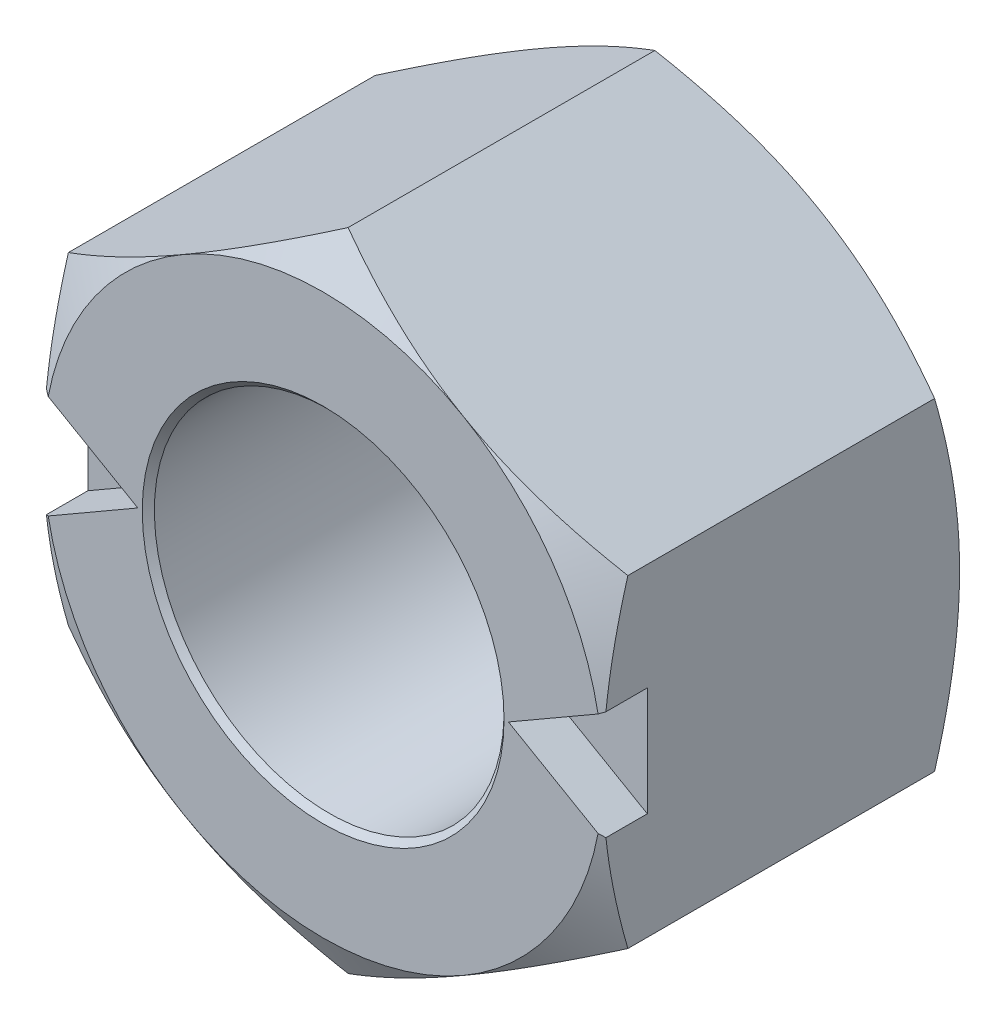
SolidWorks part; units mm, degrees
ref_plane "Front Plane" through (0, 0, 0) normal (0, 0, 1) x (1, 0, 0)
ref_plane "Top Plane" through (0, 0, 0) normal (0, 1, 0) x (1, 0, 0)
ref_plane "Right Plane" through (0, 0, 0) normal (1, 0, 0) x (0, 0, -1)
sketch "Sketch1" plane through (0, 0, 0) normal (0, 0, 1) x (1, 0, 0)
  line L0 (0.3175, 0) -> (-0.3175, 0) construction
  line L1 (0, 4.6188) -> (-4, 2.3094) construction
  line L2 (-4, 2.3094) -> (-4, -2.3094) construction
  line L3 (-4, -2.3094) -> (0, -4.6188) construction
  line L4 (0, -4.6188) -> (4, -2.3094) construction
  line L5 (4, -2.3094) -> (4, 2.3094) construction
  line L6 (4, 2.3094) -> (0, 4.6188) construction
  circle A0 centre (0, 0) radius 4 construction
  point P10 (4, 2.3094)
  point P11 (-4, 2.3094)
  point P14 (0, 0)
  point P15 (-0.3175, 0)
  point P16 (0.3175, 0)
  dimension "Hex Width" = 8
  dimension "Cut Depth" = 0.635
sketch "Sketch2" plane through (0, 0, 0) normal (1, 0, 0) x (0, 0, -1)
  line L0 (2.55, 4.6188) -> (-2.55, 4.6188) construction
  line L1 (2.55, -4.6188) -> (-2.55, -4.6188) construction
  line L3 (2.55, 0) -> (-2.55, 0) construction
  line L5 (-2.55, -2.5) -> (-2.55, 2.5) construction
  line L6 (2.55, -2.5) -> (2.55, 2.5) construction
  line L7 (-3.3, 2.5866) -> (-2.5, 2.5866) construction
  line L8 (-2.5, 2.5866) -> (-2.9, 1.8938) construction
  line L9 (-2.9, 1.8938) -> (-3.3, 2.5866) construction
  line L10 (-2.9, 1.8938) -> (-2.9, 1.9804) construction
  line L11 (-2.85, 1.9804) -> (-2.95, 1.9804) construction
  line L12 (-3.275, 2.5433) -> (-2.525, 2.5433) construction
  line L13 (-3.25, 2.5) -> (-2.55, 2.5) construction
  line L14 (-2.9, 2.5) -> (-2.9, 2.5866) construction
  line L15 (-2.55, 2.5) -> (2.55, 2.5) construction
  line L16 (-2.55, -2.5) -> (2.55, -2.5) construction
  line L17 (-2.4634, 2.5) -> (-2.55, 2.5866) construction
  line L18 (2.4634, 2.5) -> (2.55, 2.5866) construction
  line L20 (0, 4.6188) -> (0, -4.6188) construction
  point P0 (0, -4.6188)
  point P2 (0, 4.6188)
  point P4 (2.55, 4.6188)
  point P7 (0, 4.6188)
  point P8 (-2.55, 4.6188)
  point P10 (-2.55, -4.6188)
  point P13 (0, -4.6188)
  point P14 (2.55, -4.6188)
  point P15 (-2.55, 0)
  point P18 (0, 0)
  point P19 (2.55, 0)
  point P21 (-2.55, 2.5)
  point P24 (-2.55, 0)
  point P25 (-2.55, -2.5)
  point P28 (2.55, 0)
  point P29 (2.55, -2.5)
  point P30 (2.55, 2.5)
  point P37 (-2.9, 1.9804)
  point P41 (-2.9, 2.5)
  point P44 (-2.9, 2.5433)
  point P46 (-2.95, 1.9804)
  point P47 (-2.85, 1.9804)
  point P48 (-2.55, 2.5)
  point P51 (-2.4634, 2.5)
  point P52 (-2.55, 2.5866)
  point P55 (2.55, 2.5866)
  point P56 (2.4634, 2.5)
  dimension "Height" = 5.1
  dimension "Thread OD" = 5
  dimension "Pitch" = 0.8
  dimension "D1" = 0.1
  dimension "D2" = 45
ref_plane "Plane1" through (0, 0, 2.55) normal (0, 0, 1) x (1, 0, 0)
sketch "Sketch3" plane through (0, 0, 2.55) normal (0, 0, 1) x (1, 0, 0)
  line L0 (0, 0) -> (-4, 0) construction
  line L1 (0, -2.5) -> (0, 2.5) construction
  line L2 (-4, 2.3094) -> (-4, -2.3094) construction
  line L3 (0, 0) -> (0, 4.6188) construction
  line L4 (-4, -0.7794) -> (-4, 0.7794) construction
  line L5 (-4, 0.7794) -> (-2.6501, 0) construction
  line L6 (-2.6501, 0) -> (-4, -0.7794) construction
  line L7 (0, 0) -> (1.4003, -1.4003) construction
  circle A0 centre (0, 0) radius 2.5866 construction
  circle A1 centre (0, 0) radius 1.9804 construction
  point P6 (0, 1.9804)
  point P11 (-4, 0)
  point P13 (-2.5866, 0)
  point P14 (0, 2.5866)
  point P18 (-2.6501, 0)
  point P20 (1.4003, -1.4003)
  dimension "D1" = 60
  dimension "D2" = 0.0635
  dimension "D3" = 45
sketch "Sketch4" plane through (0, 0, 0) normal (0, 0, 1) x (1, 0, 0)
  line L0 (-4, 2.3094) -> (-4, -2.3094) construction
  line L1 (0, 4.6188) -> (-4, 2.3094) construction
  line L2 (-4, -2.3094) -> (0, -4.6188) construction
  line L3 (0, -4.6188) -> (4, -2.3094) construction
  line L4 (4, -2.3094) -> (4, 2.3094) construction
  line L5 (4, 2.3094) -> (0, 4.6188) construction
  line L6 (-4, 2.3094) -> (-4, -2.3094)
  line L7 (0, 4.6188) -> (-4, 2.3094)
  line L8 (-4, -2.3094) -> (0, -4.6188)
  line L9 (0, -4.6188) -> (4, -2.3094)
  line L10 (4, -2.3094) -> (4, 2.3094)
  line L11 (4, 2.3094) -> (0, 4.6188)
extrude "Boss-Extrude1" add sketch "Sketch4" along normal mid plane 5.1
sketch "Sketch5" plane through (0, 0, 2.55) normal (0, 0, 1) x (1, 0, 0)
  circle A0 centre (0, 0) radius 4 construction
  circle A1 centre (0, 0) radius 4
extrude "Cut-Extrude1" cut sketch "Sketch5" against normal through all draft 60 flip side to cut
sketch "Sketch6" plane through (0, 0, -2.55) normal (0, 0, -1) x (-1, 0, 0)
  circle A0 centre (0, 0) radius 4 construction
  circle A1 centre (0, 0) radius 4
extrude "Cut-Extrude2" cut sketch "Sketch6" against normal through all draft 60 flip side to cut
sketch "Sketch7" plane through (0, 0, 0) normal (1, 0, 0) x (0, 0, -1)
  line L1 (-2.55, -2.5) -> (-2.55, 2.5) construction
  line L6 (2.55, 0) -> (-2.55, 0)
  line L10 (-2.55, 0) -> (-2.55, 2.5866)
  line L11 (-2.55, 2.5866) -> (-2.4634, 2.5)
  line L12 (-2.4634, 2.5) -> (2.4634, 2.5)
  line L13 (2.4634, 2.5) -> (2.55, 2.5866)
  line L14 (2.55, 2.5866) -> (2.55, 0)
revolve "Cut-Revolve1" cut sketch "Sketch7" angle 360 about L6
sketch "Sketch8" plane through (0, 0, 2.55) normal (0, 0, 1) x (1, 0, 0)
  line L0 (-2.6501, 0) -> (-4, -0.7794) construction
  line L1 (-4, 0.7794) -> (-2.6501, 0) construction
  line L2 (-4, -0.7794) -> (-4, 0.7794) construction
  line L3 (-2.6501, 0) -> (-4, -0.7794)
  line L4 (-4, 0.7794) -> (-2.6501, 0)
  line L5 (-4, -0.7794) -> (-4, 0.7794)
  line L6 (0, 0) -> (0, 4.6188) construction
  line L7 (0, 0) -> (0, 4.6188) construction
  line L8 (4, -0.7794) -> (4, 0.7794)
  line L9 (4, 0.7794) -> (2.6501, 0)
  line L10 (2.6501, 0) -> (4, -0.7794)
extrude "Cut-Extrude3" cut sketch "Sketch8" against normal blind 0.635
ref_axis "Center Axis 1" through (0, 0, -2.55) along (0, 0, 1)
sketch "Sketch9" [suppressed] plane through (0, 0, 2.55) normal (0, 0, 1) x (1, 0, 0)
  circle A0 centre (0, 0) radius 2.5
curve "Helix/Spiral1" [suppressed] pitch 0.8 height 5.9 turns 7.375
sketch "Sketch10" [suppressed] plane through (0, 0, 0) normal (1, 0, 0) x (0, 0, -1)
  line L0 (-2.85, 1.9804) -> (-2.95, 1.9804) construction
  line L1 (-3.275, 2.5433) -> (-2.525, 2.5433) construction
  line L2 (-2.85, 1.9804) -> (-2.95, 1.9804)
  line L3 (-3.275, 2.5433) -> (-2.525, 2.5433)
  line L4 (-3.275, 2.5433) -> (-2.95, 1.9804)
  line L5 (-2.525, 2.5433) -> (-2.85, 1.9804)
sweep "Sweep1" [suppressed] add profiles "Sketch10" path "Helix/Spiral1"
sketch "Sketch11" [suppressed] plane through (0, 0, 2.55) normal (0, 0, 1) x (1, 0, 0)
  circle A0 centre (0, 0) radius 2.5866
  point P0 (0, 2.5866)
extrude "Cut-Extrude4" [suppressed] cut sketch "Sketch11" against normal through all draft 45 and the other way through all draft 45
sketch "Sketch12" [suppressed] plane through (0, 0, -2.55) normal (0, 0, -1) x (-1, 0, 0)
  circle A0 centre (0, 0) radius 2.5866
  point P0 (0, 2.5866)
extrude "Cut-Extrude5" [suppressed] cut sketch "Sketch12" against normal through all draft 45 and the other way through all draft 45
equation "\"D1@Sketch2\"=\"Pitch@Sketch2\"/8"
equation "\"D1@Boss-Extrude1\"=\"Height@Sketch2\""
equation "\"D3@Helix/Spiral1\"=\"Height@Sketch2\"+\"Pitch@Sketch2\""
equation "\"D4@Helix/Spiral1\"=\"Pitch@Sketch2\""
equation "\"D1@Cut-Extrude3\" = \"Cut Depth@Sketch1\""
